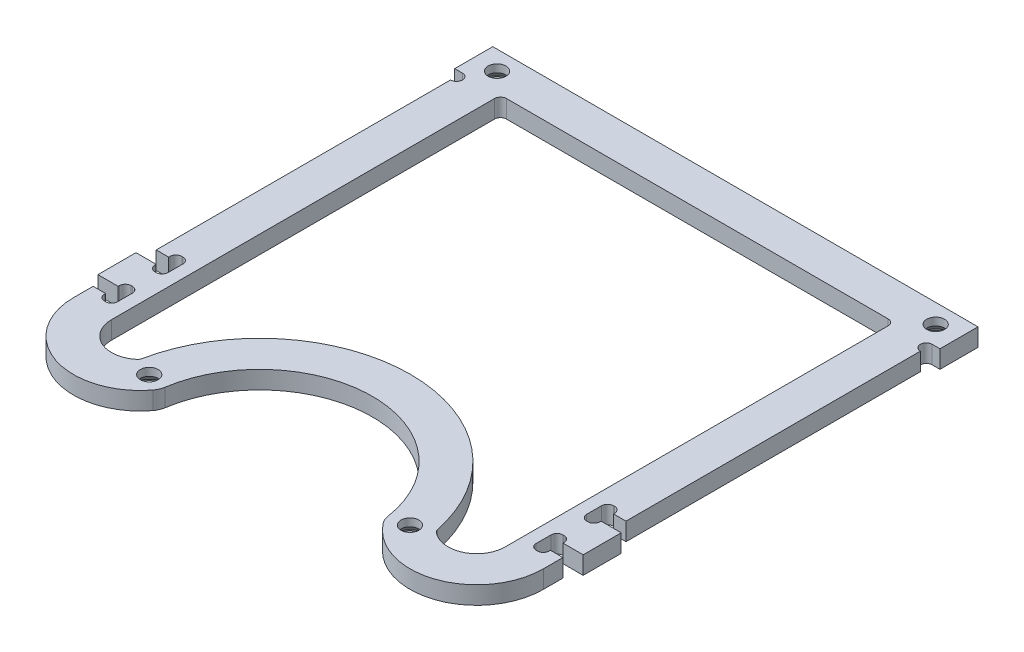
SolidWorks part; units mm, degrees
ref_plane "Front Plane" through (0, 0, 0) normal (0, 0, 1) x (1, 0, 0)
ref_plane "Top Plane" through (0, 0, 0) normal (0, 1, 0) x (1, 0, 0)
ref_plane "Right Plane" through (0, 0, 0) normal (1, 0, 0) x (0, 0, -1)
sketch "Sketch1" plane through (0, 0, 0) normal (0, 1, 0) x (1, 0, 0)
  line L0 (-36.88, 36.725) -> (36.88, 36.725) construction
  line L1 (36.88, 36.725) -> (21.92, -36.725) construction
  line L2 (21.92, -36.725) -> (-21.92, -36.725) construction
  line L3 (-21.92, -36.725) -> (-36.88, 36.725) construction
  line L4 (0, -40.095) -> (0, -36.725) construction
  line L5 (0, 36.725) -> (0, -36.725) construction
  line L6 (-39.5, -14.675) -> (-39.5, 33.525)
  line L7 (-33.1, -14.675) -> (-33.1, 33.525)
  line L8 (-39.5, 9.425) -> (-33.1, 9.425) construction
  line L9 (0, 33.525) -> (0, 39.925) construction
  line L10 (-39.5, -23.275) -> (-33.1, -23.275) construction
  line L13 (40.8, 33.525) -> (-40.8, 33.525)
  line L14 (40.8, 33.525) -> (40.8, 39.925)
  line L15 (40.8, 39.925) -> (-40.8, 39.925)
  line L16 (-40.8, 33.525) -> (-40.8, 39.925)
  line L17 (40.8, 33.525) -> (-40.8, 39.925) construction
  line L18 (40.8, 39.925) -> (-40.8, 33.525) construction
  line L19 (39.5, 33.525) -> (-39.5, 33.525)
  line L20 (39.5, 33.525) -> (39.5, 39.925)
  line L21 (39.5, 39.925) -> (-39.5, 39.925)
  line L22 (-39.5, 33.525) -> (-39.5, 39.925)
  line L23 (39.5, 33.525) -> (-39.5, 39.925) construction
  line L24 (39.5, 39.925) -> (-39.5, 33.525) construction
  line L27 (-35.2, -25.275) -> (-37.4, -25.275)
  line L28 (-39.5, -20.075) -> (-40.8, -20.075)
  line L29 (-35.2, -16.775) -> (-35.2, -14.675) construction
  line L30 (-33.1, -31.875) -> (-39.5, -31.875)
  line L31 (-33.1, -31.875) -> (-33.1, -14.675)
  line L32 (-33.1, -14.675) -> (-39.5, -14.675)
  line L33 (-39.5, -31.875) -> (-39.5, -14.675)
  line L34 (-33.1, -31.875) -> (-39.5, -14.675) construction
  line L35 (-33.1, -14.675) -> (-39.5, -31.875) construction
  line L36 (-39.5, -20.075) -> (-37.4, -20.075)
  line L37 (-39.5, -20.075) -> (-39.5, -17.975)
  line L38 (-39.5, -17.975) -> (-37.4, -17.975)
  line L39 (-37.4, -20.075) -> (-37.4, -17.975)
  line L40 (-37.4, -19.025) -> (-39.5, -19.025) construction
  line L41 (-37.4, -19.025) -> (-33.1, -19.025) construction
  line L42 (-36.3, -31.875) -> (-36.3, -14.675) construction
  line L43 (-35.2, -21.275) -> (-37.4, -21.275)
  line L44 (-35.2, -21.275) -> (-35.2, -16.775)
  line L45 (-35.2, -16.775) -> (-37.4, -16.775)
  line L46 (-37.4, -21.275) -> (-37.4, -16.775)
  line L47 (-35.2, -21.275) -> (-37.4, -16.775) construction
  line L48 (-35.2, -16.775) -> (-37.4, -21.275) construction
  line L53 (-35.2, -25.275) -> (-35.2, -29.775)
  line L58 (-35.2, -29.775) -> (-37.4, -29.775)
  line L67 (39.5, -17.975) -> (37.4, -17.975)
  line L68 (-37.4, -25.275) -> (-37.4, -29.775)
  line L69 (-39.5, -28.575) -> (-37.4, -28.575)
  line L70 (-39.5, -20.075) -> (-39.5, -26.475)
  line L71 (-39.5, -26.475) -> (-40.8, -26.475)
  line L72 (-40.8, -20.075) -> (-40.8, -26.475)
  line L73 (-39.5, -20.075) -> (-40.8, -26.475) construction
  line L74 (-39.5, -26.475) -> (-40.8, -20.075) construction
  line L75 (-39.5, -26.475) -> (-37.4, -26.475)
  line L76 (39.5, -20.075) -> (37.4, -20.075)
  line L77 (39.5, -28.575) -> (37.4, -28.575)
  line L78 (39.5, -26.475) -> (37.4, -26.475)
  line L79 (37.4, -25.275) -> (37.4, -29.775)
  line L80 (35.2, -29.775) -> (37.4, -29.775)
  line L81 (35.2, -25.275) -> (35.2, -29.775)
  line L82 (35.2, -25.275) -> (37.4, -25.275)
  line L83 (35.2, -21.275) -> (37.4, -21.275)
  line L84 (35.2, -21.275) -> (35.2, -16.775)
  line L85 (35.2, -16.775) -> (37.4, -16.775)
  line L86 (37.4, -21.275) -> (37.4, -16.775)
  line L87 (39.5, -17.975) -> (37.4, -17.975)
  line L88 (39.5, -20.075) -> (40.8, -20.075)
  line L89 (40.8, -20.075) -> (40.8, -26.475)
  line L90 (39.5, -26.475) -> (40.8, -26.475)
  line L91 (39.5, -31.875) -> (39.5, -14.675)
  line L92 (33.1, -31.875) -> (33.1, -14.675)
  line L93 (33.1, -14.675) -> (33.1, 33.525)
  line L94 (39.5, -14.675) -> (39.5, 33.525)
  circle A0 centre (21.92, -36.725) radius 1.5
  circle A1 centre (-21.92, -36.725) radius 1.5
  circle A2 centre (-36.88, 36.725) radius 1.5
  circle A3 centre (36.88, 36.725) radius 1.5
  circle A4 centre (-36.88, 36.725) radius 3.2
  circle A5 centre (-21.92, -36.725) radius 3.2
  circle A6 centre (21.92, -36.725) radius 3.2
  circle A7 centre (36.88, 36.725) radius 3.2
  circle A8 centre (0, -40.095) radius 16
  circle A9 centre (0, -40.095) radius 25.3775
  circle A10 centre (0, -40.095) radius 18.9775
  arc A11 (-39.5, -31.875) -> (-19.3737, -38.6631) centre (-28.2921, -31.875) ccw
  arc A12 (-33.1, -31.875) -> (-24.4663, -34.7869) centre (-28.2921, -31.875) ccw
  arc A13 (33.1, -31.875) -> (24.4663, -34.7869) centre (28.2921, -31.875) cw
  arc A14 (39.5, -31.875) -> (19.3737, -38.6631) centre (28.2921, -31.875) cw
  circle A15 centre (-39.5, 32.525) radius 1
  circle A16 centre (39.5, 32.525) radius 1
  point P10 (0, 0)
  point P26 (0, -23.275)
  point P29 (-40.15, -23.275)
  point P37 (-36.3, -23.275)
  point P53 (-36.3, -19.025)
  dimension "D4" = 3
  dimension "D5" = 6.4
  dimension "D6" = 32
  dimension "D11" = 2
  dimension "D1" = 74.958
  dimension "D2" = 43.84
  dimension "D3" = 73.76
  dimension "D7" = 3.37
  dimension "D8" = 81.6
  dimension "D9" = 60
  dimension "D10" = 79
  dimension "D12" = 2.1
  dimension "D13" = 2.2
  dimension "D14" = 4.5
extrude "Shape" add sketch "Sketch1" along normal blind 3 contours A13 A9 A12 A5 A10 A6 | A5 A1 | A9 A11 A5 | A12 A9 A5 | A12 L30 A11 A9 | L33 L75 L68 L27 L53 L58 L69 L30 L31 L32 L38 L46 L45 L44 L43 L36 | L28 L72 L71 L33 | A15 L6 L32 L7 L13 L19 | A4 L22 L15 L16 L13 | A4 L21 L22 | A4 L22 A2 | L22 A4 | A4 L22 L19 | A7 L21 A4 L13 L19 | A7 L20 A3 | A7 L20 L13 L14 L15 | L20 A7 | A7 L13 L20 | L94 A16 L13 L19 L93 L92 A13 A9 A14 L91 L77 L79 L80 L81 L82 L78 L76 L86 L83 L84 L85 L67 | A7 L20 L15 | L91 L90 L89 L88 | A9 A13 A6 | A6 A0 | A14 A9 A6 region at (-36.2858, 0, -9.3068) region at (-36.0672, 0, 23.275) region at (-38.8761, 0, -33.9129) region at (-40.2377, 0, -36.725) region at (0, 0, -36.725) region at (-32.2904, 0, 37.7071) region at (-40.15, 0, 23.275) region at (-38.3167, 0, -33.9628) region at (-39.7339, 0, -36.725) region at (35.4284, 0, 5.7836) region at (-24.8633, 0, 35.4035) region at (0, 0, 15.2643) region at (-38.8761, 0, -39.5371) region at (38.8761, 0, -33.9129) region at (33.7665, 0, -36.725) region at (-23.7462, 0, 40.4359) region at (24.8633, 0, 35.4035) region at (-24.7821, 0, 35.5096) region at (40.2377, 0, -36.725) region at (38.8761, 0, -39.5371) region at (39.7339, 0, -36.725) region at (23.7462, 0, 40.4359) region at (25.0204, 0, 36.4881) region at (40.15, 0, 23.275)
fillet "Mill fillets" radius 1 20 edges at (37.4, 1.5, 21.275) (35.2, 1.5, 21.275) (35.2, 1.5, 16.775) (37.4, 1.5, 16.775) (37.4, 1.5, 25.275) (35.2, 1.5, 25.275) (37.4, 1.5, 29.775) (35.2, 1.5, 29.775) (-37.4, 1.5, 21.275) (-35.2, 1.5, 21.275) (-35.2, 1.5, 16.775) (-37.4, 1.5, 16.775) (-37.4, 1.5, 25.275) (-35.2, 1.5, 25.275) (-35.2, 1.5, 29.775) (-37.4, 1.5, 29.775) (-24.921, 1.5, 35.303) (24.921, 1.5, 35.303) (33.1, 1.5, -33.525) (-33.1, 1.5, -33.525)
hole_wizard "M3 countersunks" positions "Sketch2" profile "Sketch3" countersink size "M3" standard "ANSI Metric" end condition through all
sketch "Sketch2" plane through (0, 0, 0) normal (0, -1, 0) x (-1, 0, 0)
  point P0 (21.92, -36.725)
  point P3 (-21.92, -36.725)
  point P6 (-36.88, 36.725)
  point P9 (36.88, 36.725)
sketch "Sketch3" plane through (-21.92, 0, 36.725) normal (1, 0, 0) x (0, 0, -1)
  line L0 (0, 0) -> (0, 3)
  line L1 (0, 3) -> (1.5, 3)
  line L2 (1.5, 3) -> (1.5, 1.7)
  line L3 (1.5, 1.7) -> (3, 0.2)
  line L4 (3, 0.2) -> (3, 0)
  line L6 (3, 0) -> (0, 0)
  line L7 (-1.5, 1.7) -> (-3, 0.2) construction
  line L11 (0, -6.35) -> (0, 107.95) construction
  dimension "Thru Hole Dia." = 3
  dimension "Thru Hole Depth" = 3
  dimension "C'Sink Dia." = 6
  dimension "C'Sink Angle" = 90
  dimension "Head Clearance" = 0.2
sketch "Sketch4" plane through (-39.5, 0, 0) normal (-1, 0, 0) x (0, 0, 1)
  line L0 (17.975, 3) -> (20.075, 0) construction
  line L1 (28.575, 0) -> (26.475, 3) construction
  point P8 (19.025, 1.5)
  point P9 (27.525, 1.5)
ref_axis "Tap axis 1" through (-50.6169, 1.5, 19.025) along (1, 0, 0)
ref_axis "Tap axis 2" through (-50.8013, 1.5, 27.525) along (1, 0, 0)
